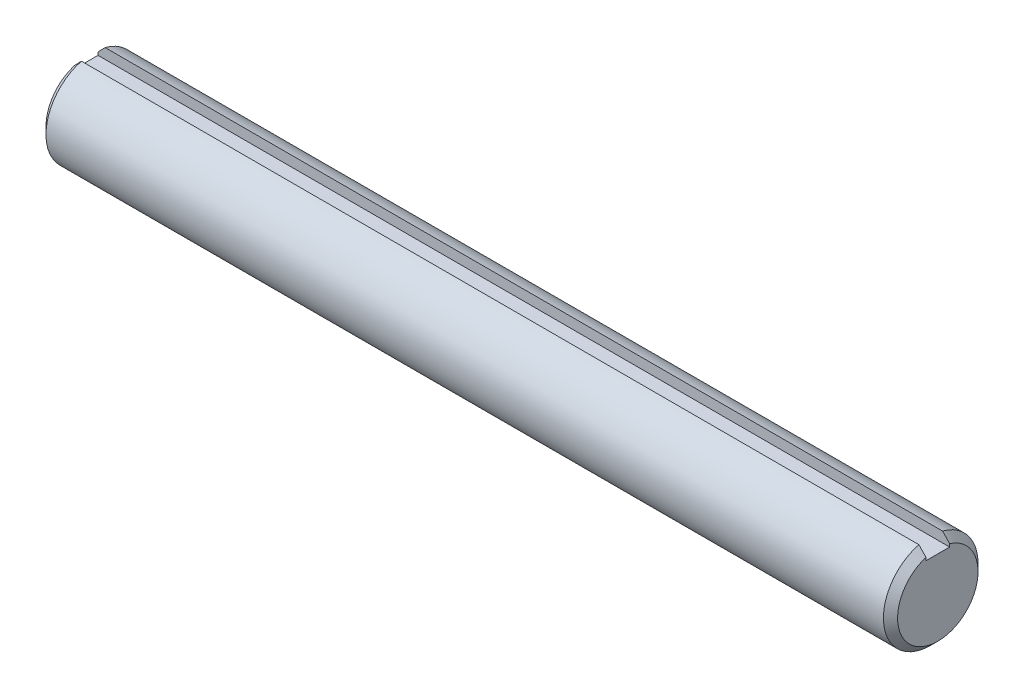
SolidWorks part; units mm, degrees
material "AISI 1045 Steel, cold drawn"
ref_plane "Front" through (0, 0, 0) normal (0, 0, 1) x (1, 0, 0)
ref_plane "Top" through (0, 0, 0) normal (0, 1, 0) x (1, 0, 0)
ref_plane "Right" through (0, 0, 0) normal (1, 0, 0) x (0, 0, -1)
sketch "Sketch1" plane through (0, 0, 0) normal (1, 0, 0) x (0, 0, -1)
  circle A0 centre (0, 0) radius 12.7
  dimension "dia" = 25.4
extrude "Extrude1" add sketch "Sketch1" along normal mid plane 228.6
sketch "Sketch2" plane through (0, 0, 0) normal (0, 0, 1) x (1, 0, 0)
  point P0 (114.3, 12.7)
  point P1 (-114.3, 12.7)
  point P2 (-114.3, -12.7)
chamfer "Chamfer1" distance 1.905 angle 45 2 edges at (-114.3, 0, -12.7) (114.3, 0, -12.7)
sketch "Sketch3" plane through (0, 0, 0) normal (1, 0, 0) x (0, 0, -1)
  line L1 (-3.175, 12.7) -> (3.175, 12.7)
  line L2 (-3.175, 12.7) -> (-3.175, 9.525)
  line L3 (-3.175, 9.525) -> (3.175, 9.525)
  line L4 (3.175, 12.7) -> (3.175, 9.525)
  dimension "key wd" = 6.35
  dimension "key dp" = 3.175
extrude "Extrude2" cut sketch "Sketch3" against normal through all and the other way through all
equation "\"D1@Chamfer1\" = \"dia@Sketch1\" * .075"
